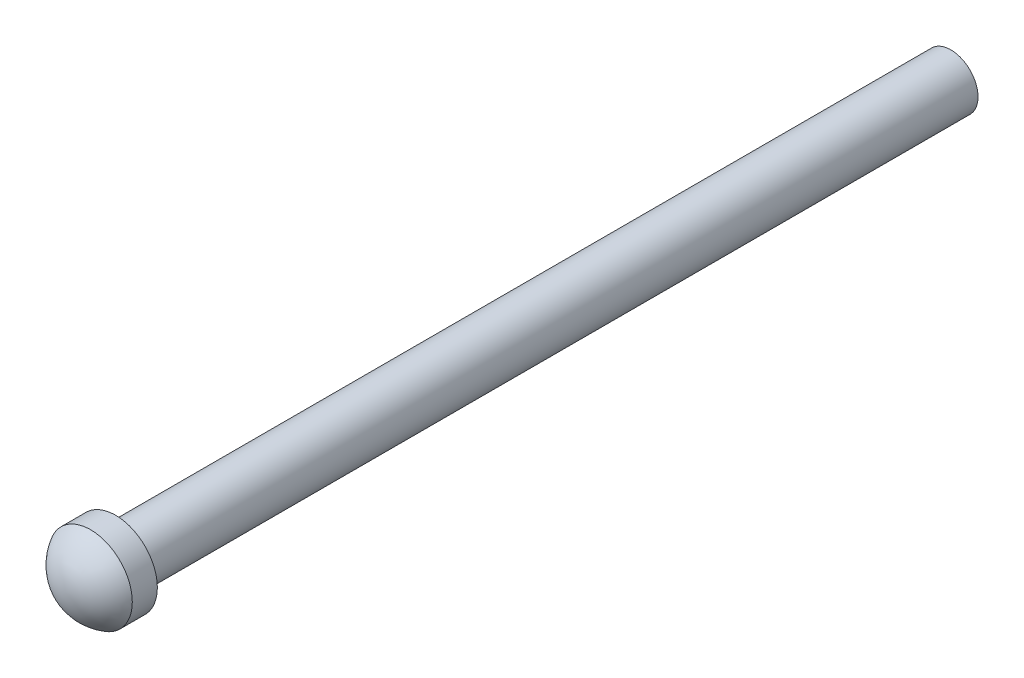
SolidWorks part; units mm, degrees
ref_plane "Front Plane" through (0, 0, 0) normal (0, 0, 1) x (1, 0, 0)
ref_plane "Top Plane" through (0, 0, 0) normal (0, 1, 0) x (1, 0, 0)
ref_plane "Right Plane" through (0, 0, 0) normal (1, 0, 0) x (0, 0, -1)
sketch "Sketch1" plane through (0, 0, 0) normal (0, 0, 1) x (1, 0, 0)
  circle A2 centre (5, 60) radius 3.25
  circle A3 centre (5, 60) radius 3.25
  dimension "D1" = 0.25
sketch "Sketch2" plane through (0, 0, 0) normal (1, 0, 0) x (0, 0, -1)
  line L0 (0, 0) -> (100, 0) construction
  line L1 (0, 0) -> (100, 0)
sweep "Sweep1" add profiles "Sketch1" path "Sketch2"
sketch "Sketch3" plane through (0, 0, 0) normal (0, 0, 1) x (1, 0, 0)
  circle A0 centre (5, 60) radius 5
  arc A1 (5, 55) -> (0, 60) centre (5, 60) ccw construction
extrude "Boss-Extrude1" add sketch "Sketch3" along normal blind 3
dome "Dome1" faces to dome 1 distance 3 reverse direction no elliptical dome no face at (10, 60, 3) parameters "D1"=3
